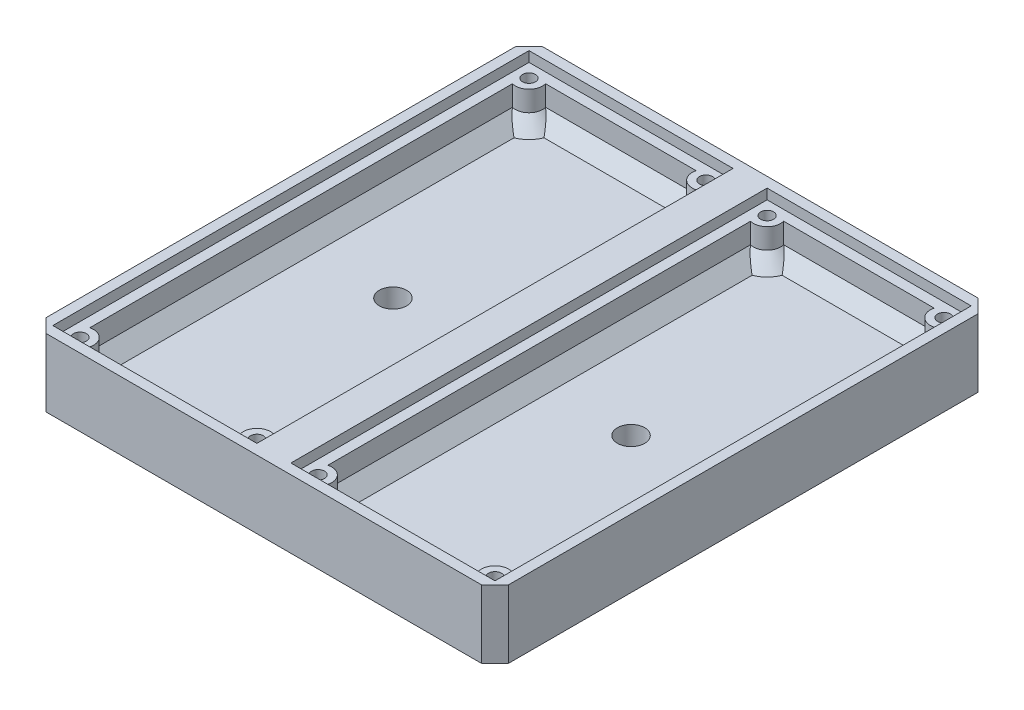
SolidWorks part; units mm, degrees
ref_plane "Front Plane" through (0, 0, 0) normal (0, 0, 1) x (1, 0, 0)
ref_plane "Top Plane" through (0, 0, 0) normal (0, 1, 0) x (1, 0, 0)
ref_plane "Right Plane" through (0, 0, 0) normal (1, 0, 0) x (0, 0, -1)
sketch "Sketch2" plane through (0, 0, 0) normal (0, 1, 0) x (1, 0, 0)
  line L1 (-34, -36.5) -> (34, -36.5)
  line L2 (-34, -36.5) -> (-34, 36.5)
  line L3 (-34, 36.5) -> (34, 36.5)
  line L4 (34, -36.5) -> (34, 36.5)
  line L5 (-34, -36.5) -> (34, 36.5) construction
  line L6 (-34, 36.5) -> (34, -36.5) construction
  line L7 (-32.5, -35) -> (-2.5, -35)
  line L8 (-32.5, -35) -> (-32.5, 35)
  line L9 (-32.5, 35) -> (-2.5, 35)
  line L10 (-2.5, -35) -> (-2.5, 35)
  line L11 (-32.5, -35) -> (-2.5, 35) construction
  line L12 (-32.5, 35) -> (-2.5, -35) construction
  line L13 (2.5, -35) -> (32.5, -35)
  line L14 (2.5, -35) -> (2.5, 35)
  line L15 (2.5, 35) -> (32.5, 35)
  line L16 (32.5, -35) -> (32.5, 35)
  line L17 (2.5, -35) -> (32.5, 35) construction
  line L18 (2.5, 35) -> (32.5, -35) construction
  point P0 (0, 0)
  point P6 (-17.5, 0)
  point P11 (17.5, 0)
  dimension "D1" = 68
  dimension "D2" = 30
  dimension "D3" = 30
  dimension "D4" = 1.5
  dimension "D5" = 1.5
  dimension "D6" = 1.5
  dimension "D7" = 70
  dimension "D8" = 1.5
extrude "Boss-Extrude1" add sketch "Sketch2" against normal blind 10 contours L7 L10 L9 L8 | L13 L16 L15 L14 | L1 L4 L3 L2 L16 L13 L14 L15 L10 L7 L8 L9 | L2 L1 L4 L3 region at (0, 0, 0) region at (-17.5, 0, 0) region at (17.5, 0, 0)
extrude "Cut-Extrude2" cut sketch "Sketch2<3>" against normal blind 1.5 contours L7 L10 L9 L8 | L13 L16 L15 L14 region at (-17.5, 0, 0) region at (17.5, 0, 0)
sketch "Sketch2<3>" plane through (0, 0, 0) normal (0, 1, 0) x (1, 0, 0) same geometry as "Sketch2"
sketch "Sketch3" plane through (0, -1.5, 0) normal (0, 1, 0) x (1, 0, 0)
  line L8 (-31, -33.5) -> (-4, -33.5)
  line L9 (-4, -33.5) -> (-4, 33.5)
  line L10 (-4, 33.5) -> (-31, 33.5)
  line L11 (-31, 33.5) -> (-31, -33.5)
  line L12 (-31, -33.5) -> (-4, -33.5)
  line L13 (-4, -33.5) -> (-4, 33.5)
  line L14 (-4, 33.5) -> (-31, 33.5)
  line L15 (-31, 33.5) -> (-31, -33.5)
  line L20 (4, -33.5) -> (31, -33.5)
  line L21 (31, -33.5) -> (31, 33.5)
  line L22 (31, 33.5) -> (4, 33.5)
  line L23 (4, 33.5) -> (4, -33.5)
  line L24 (4, -33.5) -> (31, -33.5)
  line L25 (31, -33.5) -> (31, 33.5)
  line L26 (31, 33.5) -> (4, 33.5)
  line L27 (4, 33.5) -> (4, -33.5)
  dimension "D1" = 1.5
  dimension "D2" = 1.5
extrude "Cut-Extrude3" cut sketch "Sketch3" against normal blind 5
sketch "Sketch4" plane through (0, -6.5, 0) normal (0, 1, 0) x (1, 0, 0)
  line L0 (-4, 33.5) -> (-31, 33.5) construction
  line L1 (-4.5, -33) -> (-30.5, -33) construction
  line L2 (-4.5, -33) -> (-4.5, 33) construction
  line L3 (-4.5, 33) -> (-30.5, 33) construction
  line L4 (-30.5, -33) -> (-30.5, 33) construction
  line L5 (-4.5, -33) -> (-30.5, 33) construction
  line L6 (-4.5, 33) -> (-30.5, -33) construction
  line L7 (0, -55) -> (0, 55) construction
  line L8 (4.5, 33) -> (30.5, -33) construction
  line L9 (4.5, -33) -> (30.5, 33) construction
  line L10 (30.5, -33) -> (30.5, 33) construction
  line L11 (4.5, 33) -> (30.5, 33) construction
  line L12 (4.5, -33) -> (4.5, 33) construction
  line L13 (4.5, -33) -> (30.5, -33) construction
  circle A0 centre (-30.5, 33) radius 2
  circle A1 centre (-4.5, 33) radius 2
  circle A2 centre (-4.5, -33) radius 2
  circle A3 centre (-30.5, -33) radius 2
  circle A4 centre (30.5, -33) radius 2
  circle A5 centre (4.5, -33) radius 2
  circle A6 centre (4.5, 33) radius 2
  circle A7 centre (30.5, 33) radius 2
  point P0 (-17.5, 0)
  point P7 (-17.5, 33.5)
  point P24 (17.5, 0)
  dimension "D3" = 4
  dimension "D1" = 26
  dimension "D2" = 66
  dimension "D4" = 2
  dimension "D5" = 2
extrude "Boss-Extrude2" add sketch "Sketch4" along normal up to surface (5 mm away) up to face at (-17.5, -1.5, 0)
sketch "Sketch5" plane through (0, -1.5, 0) normal (0, 1, 0) x (1, 0, 0)
  line L0 (-30.5, 33) -> (-4.5, 33) construction
  line L1 (-30.5, 33) -> (-30.5, -33) construction
  line L2 (0, -55) -> (0, 55) construction
  line L3 (30.5, 33) -> (30.5, -33) construction
  line L4 (30.5, 33) -> (4.5, 33) construction
  circle A0 centre (-30.5, 33) radius 0.95
  circle A1 centre (-4.5, 33) radius 0.95
  circle A2 centre (-4.5, -33) radius 0.95
  circle A3 centre (-30.5, -33) radius 0.95
  circle A4 centre (30.5, -33) radius 0.95
  circle A5 centre (4.5, -33) radius 0.95
  circle A6 centre (4.5, 33) radius 0.95
  circle A7 centre (30.5, 33) radius 0.95
  dimension "D1" = 1.9
  dimension "D4" = 26
  dimension "D5" = 66
  dimension "D2" = 2
  dimension "D3" = 2
extrude "Cut-Extrude4" cut sketch "Sketch5" along normal up to surface (1.5 mm away) and the other way up to surface (5 mm away) up to face at (-17.5, 0, 0) other way up to face at (-17.5, -6.5, 0)
chamfer "Chamfer1" distance 2 angle 45 4 edges at (34, -5, -36.5) (-34, -5, -36.5) (34, -5, 36.5) (-34, -5, 36.5)
chamfer "Chamfer2" distance 2 angle 45 16 edges at (29.0858, -6.5, 31.5858) (17.5, -6.5, 33.5) (5.9142, -6.5, 31.5858) (4, -6.5, 0) (5.9142, -6.5, -31.5858) (17.5, -6.5, -33.5) (29.0858, -6.5, -31.5858) (31, -6.5, 0) (-29.0858, -6.5, -31.5858) (-17.5, -6.5, -33.5) (-5.9142, -6.5, -31.5858) (-4, -6.5, 0) (-5.9142, -6.5, 31.5858) (-17.5, -6.5, 33.5) (-29.0858, -6.5, 31.5858) (-31, -6.5, 0)
sketch "Sketch6" plane through (0, -10, 0) normal (0, -1, 0) x (1, 0, 0)
  line L0 (-28.5635, -33.5) -> (-6.4365, -33.5) construction
  line L1 (28.5635, -33.5) -> (6.4365, -33.5) construction
  circle A0 centre (-17.5, 0) radius 2
  circle A1 centre (17.5, 0) radius 2
  point P6 (-17.5, -33.5)
  point P9 (17.5, -33.5)
  point P10 (0, 0)
  dimension "D1" = 4
  dimension "D2" = 4
extrude "Cut-Extrude5" cut sketch "Sketch6" against normal blind 4
